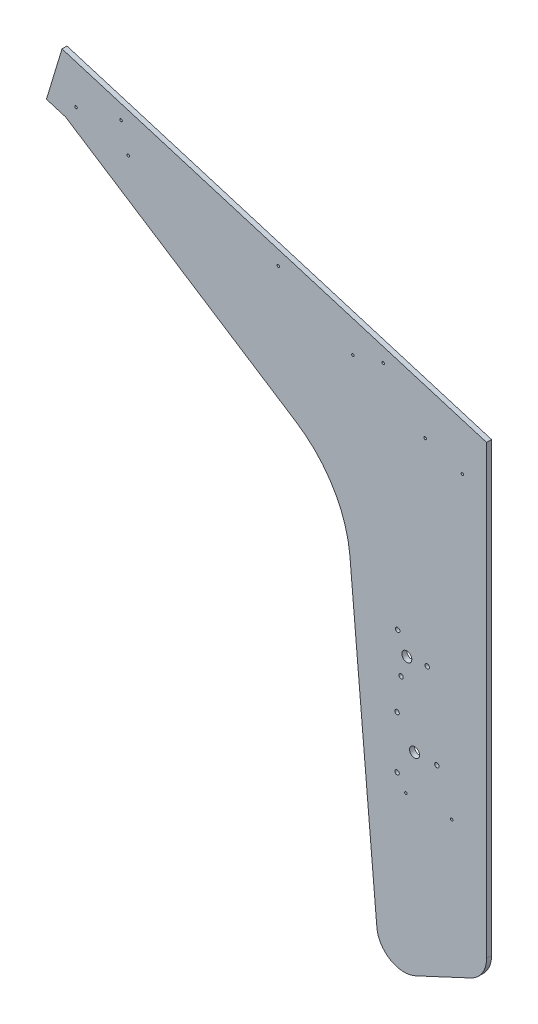
SolidWorks part; units mm, degrees
material "Beech"
ref_plane "Front Plane" through (0, 0, 0) normal (0, 0, 1) x (1, 0, 0)
ref_plane "Top Plane" through (0, 0, 0) normal (0, 1, 0) x (1, 0, 0)
ref_plane "Right Plane" through (0, 0, 0) normal (1, 0, 0) x (0, 0, -1)
sketch "Sketch1" plane through (0, 0, 0) normal (0, 0, 1) x (1, 0, 0)
  line L0 (-396.462, 396.5071) -> (138.3789, 234.6347) construction
  line L1 (134.7, 222.4793) -> (134.7, -217.5629) construction
  line L14 (-35.9297, 42.1538) -> (-1.5139, -351.2208)
  line L15 (48.0382, -379.8296) -> (118.2139, -347.1062)
  line L16 (138.3789, -315.4534) -> (138.3789, 254.5381)
  line L17 (138.3789, 254.5381) -> (-403.0991, 418.4193)
  line L18 (-403.0991, 418.4193) -> (-422.935, 352.8794)
  line L19 (-422.935, 352.8794) -> (-398.6241, 345.5216)
  line L20 (-398.6241, 345.5216) -> (-105.0266, 156.03)
  arc A6 (-35.9297, 42.1538) -> (-105.0266, 156.03) centre (-187.6695, 27.9835) ccw
  arc A7 (-1.5139, -351.2208) -> (48.0382, -379.8296) centre (33.2782, -348.1768) ccw
  arc A8 (118.2139, -347.1062) -> (138.3789, -315.4534) centre (103.4539, -315.4534) ccw
  dimension "D5" = 34.925
  dimension "D6" = 34.925
  dimension "D11" = 152.4
  dimension "D1" = 115
  dimension "D2" = 70
  dimension "D3" = 16
  dimension "D4" = 19.05
  dimension "D7" = 569.9915
  dimension "D8" = 602.715
  dimension "D9" = 34.925
  dimension "D10" = 105.1007
  dimension "D13" = 25.4
  dimension "D14" = 326.0484
  dimension "D15" = 226.5547
  dimension "D16" = 139.8928
  dimension "D17" = 77.4303
extrude "Boss-Extrude1" add sketch "Sketch1" along normal blind 6.35
hole_wizard "#10 Clearance Hole1" positions "Sketch3" profile "Sketch4" hole size "#10" standard "ANSI Inch" end condition through all
sketch "Sketch3" plane through (0, 0, 0) normal (0, 0, -1) x (-1, 0, 0)
  point P0 (-24.2517, -100.3519)
  point P3 (-24.2517, -167.0269)
  point P6 (-75.0517, -133.6894)
  point P9 (-29.3174, -58.2747)
  point P12 (-25.0263, -9.2271)
  point P15 (-62.6488, -30.6471)
sketch "Sketch4" plane through (24.2517, -100.3519, 0) normal (1, 0, 0) x (0, 1, 0)
  line L0 (0, 0) -> (0, 6.35)
  line L1 (0, 6.35) -> (2.8067, 6.35)
  line L2 (2.8067, 6.35) -> (2.8067, 0)
  line L5 (2.8067, 0) -> (0, 0)
  line L11 (0, -6.35) -> (0, 107.95) construction
  dimension "Thru Hole Dia." = 5.6134
  dimension "Thru Hole Depth" = 6.35
sketch "Sketch2" plane through (0, 0, 0) normal (0, 0, -1) x (-1, 0, 0)
  line L0 (-2.0267, -133.6894) -> (-59.1767, -133.6894) construction
  line L1 (-2.0267, -115.5093) -> (-2.0267, -151.8694) construction
  line L2 (-59.1767, -116.3297) -> (-59.1767, -151.0491) construction
  line L3 (-29.3174, -58.2747) -> (-25.0263, -9.2271) construction
  line L4 (-27.1718, -33.7509) -> (-62.6488, -30.6471) construction
  circle A0 centre (-46.4767, -133.6894) radius 6.35
  circle A1 centre (-36.6606, -32.9207) radius 6.35
  circle A2 centre (-24.2517, -100.3519) radius 2.8067 construction
  point P7 (-2.0267, -133.6894)
  point P11 (-59.1767, -133.6894)
  dimension "D1" = 12.7
  dimension "D2" = 12.7
  dimension "D3" = 22.225
  dimension "D4" = 9.525
extrude "Cut-Extrude1" cut sketch "Sketch2" against normal through all
hole_wizard "Hole1" positions "Sketch5" profile "Sketch6" legacy
sketch "Sketch5" plane through (280.9657, -208.179, 12.7) normal (0, 0, 1) x (-0.09, 0.9959, 0)
  line L0 (47.5949, 261.3648) -> (37.7623, 152.508) construction
  line L6 (451.4691, 193.1171) -> (418.4769, 118.1196) construction
  line L11 (486.2923, 274.2447) -> (514.0528, 264.0879) construction
  line L16 (472.4376, 447.6352) -> (491.8067, 432.4853) construction
  line L19 (635.9114, 629.7221) -> (595.5648, 529.8608) construction
  line L24 (664.0363, 618.3589) -> (454.7061, 100.2486) construction
  line L28 (664.0363, 618.3589) -> (611.7037, 488.8313)
  line L29 (611.7037, 488.8313) -> (559.3712, 359.3037)
  line L30 (559.3712, 359.3037) -> (507.0387, 229.7761)
  line L31 (507.0387, 229.7761) -> (454.7061, 100.2486)
  point P12 (45.8811, 242.3921)
  point P14 (40.6185, 184.1293)
  point P29 (426.1478, 135.557)
  point P31 (446.3552, 181.4922)
  point P48 (500.1726, 269.1663)
  point P79 (628.7751, 612.0592)
  point P81 (602.701, 547.5236)
  point P98 (559.3712, 359.3037)
  point P100 (507.0387, 229.7761)
  point P112 (637.87, 553.5951)
  point P120 (0, 0)
  dimension "D1" = 19.05
  dimension "D2" = 31.75
  dimension "D3" = 12.7
  dimension "D4" = 19.05
  dimension "D5" = 19.05
  dimension "D6" = 19.05
sketch "Sketch6" plane through (-327.7674, 377.3035, 12.7) normal (1, 0, 0) x (0, -1, 0)
  line L0 (0, 0) -> (0, 32.7039)
  line L1 (0, 32.7039) -> (1.5875, 31.75)
  line L2 (1.5875, 31.75) -> (1.5875, 4.0177)
  line L3 (1.5875, 4.0177) -> (5.08, 0)
  line L4 (5.08, 0) -> (0, 0)
  line L5 (0, -14.3089) -> (0, 102.4216) construction
  line L6 (0, 32.7039) -> (-1.5875, 31.75) construction
  line L7 (-1.5875, 4.0177) -> (-5.08, 0) construction
  dimension "Diameter" = 3.175
  dimension "Depth" = 31.75
  dimension "C-Sink Diameter" = 10.16
  dimension "C-Sink Angle" = 82
  dimension "Drill Angle" = 118
